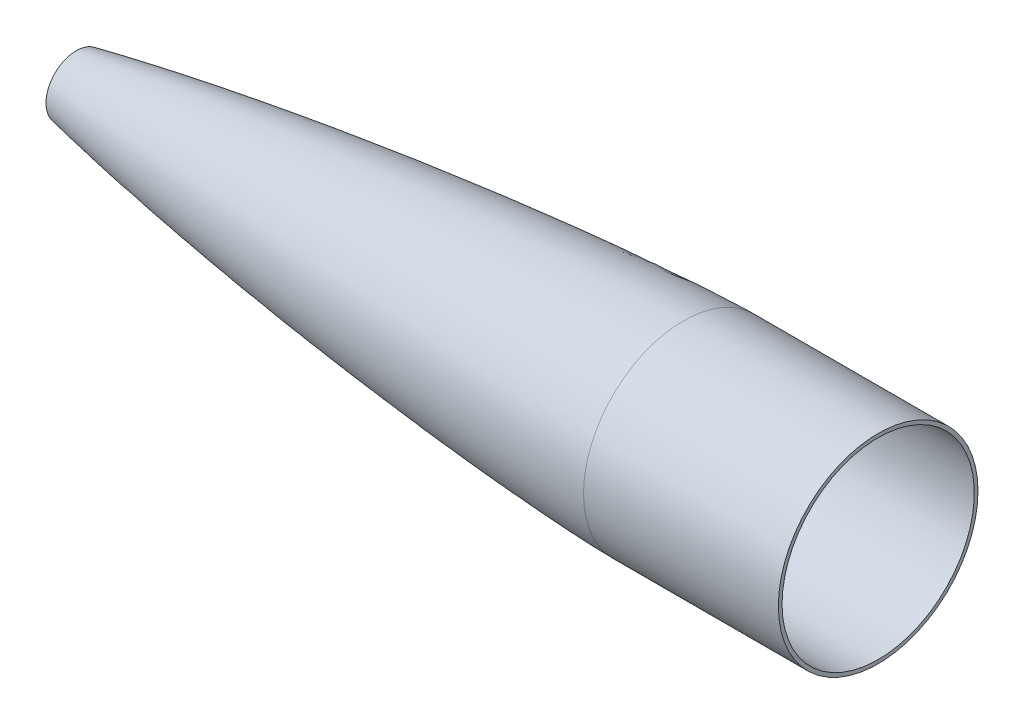
SolidWorks part; units mm, degrees
material "G12 Fiberglass"
ref_plane "Front Plane" through (0, 0, 0) normal (0, 0, 1) x (1, 0, 0)
ref_plane "Top Plane" through (0, 0, 0) normal (0, 1, 0) x (1, 0, 0)
ref_plane "Right Plane" through (0, 0, 0) normal (1, 0, 0) x (0, 0, -1)
sketch "Sketch1" plane through (0, 0, 0) normal (0, 0, 1) x (1, 0, 0)
  line L1 (0, 0) -> (294.4368, 0)
  line L6 (294.4368, 0) -> (374.4614, 0)
  line L7 (374.4614, 0) -> (374.4614, 41.1)
  line L8 (374.4614, 41.1) -> (294.2481, 41.1)
  spline S0 degree 4 poles (0, 0) (0.0018, 0.0062) (0.0065, 0.0183) (0.02, 0.0405) (0.0516, 0.0816) (0.098, 0.1304) (0.1591, 0.1863) (0.2472, 0.2588) (0.369, 0.3497) (0.5547, 0.4751) (0.869, 0.666) (1.3994, 0.9536) (2.3272, 1.3982) (4.009, 2.1055) (7.0408, 3.2125) (12.0632, 4.8001) (21.111, 7.2896) (33.8929, 10.3082) (49.7554, 13.609) (67.9644, 16.9948) (86.2568, 20.0969) (104.5881, 22.9593) (122.9505, 25.6145) (141.3391, 28.0808) (159.7506, 30.3703) (178.1826, 32.4881) (196.6334, 34.4348) (215.102, 36.2057) (233.5875, 37.7898) (252.0898, 39.1673) (267.7728, 40.127) (279.7318, 40.6956) (287.9596, 40.9757) (291.5527, 41.062) (293.3496, 41.093) (294.2481, 41.1) knots 0 0 0 0 0 0.000087 0.000174 0.000347 0.000695 0.00099 0.001284 0.001879 0.002733 0.003996 0.006219 0.009974 0.016536 0.028475 0.049524 0.080651 0.142462 0.204716 0.266969 0.329223 0.391477 0.453731 0.515984 0.578238 0.640492 0.702745 0.764999 0.827253 0.889506 0.95176 0.97588 0.98794 1 1 1 1 1 construction
  spline S1 degree 4 poles (0, 0) (0.0018, 0.0062) (0.0065, 0.0183) (0.02, 0.0405) (0.0516, 0.0816) (0.098, 0.1304) (0.1591, 0.1863) (0.2472, 0.2588) (0.369, 0.3497) (0.5547, 0.4751) (0.869, 0.666) (1.3994, 0.9536) (2.3272, 1.3982) (4.009, 2.1055) (7.0408, 3.2125) (12.0632, 4.8001) (21.111, 7.2896) (33.8929, 10.3082) (49.7554, 13.609) (67.9644, 16.9948) (86.2568, 20.0969) (104.5881, 22.9593) (122.9505, 25.6145) (141.3391, 28.0808) (159.7506, 30.3703) (178.1826, 32.4881) (196.6334, 34.4348) (215.102, 36.2057) (233.5875, 37.7898) (252.0898, 39.1673) (267.7728, 40.127) (279.7318, 40.6956) (287.9596, 40.9757) (291.5527, 41.062) (293.3496, 41.093) (294.2481, 41.1) knots 0 0 0 0 0 0.000087 0.000174 0.000347 0.000695 0.00099 0.001284 0.001879 0.002733 0.003996 0.006219 0.009974 0.016536 0.028475 0.049524 0.080651 0.142462 0.204716 0.266969 0.329223 0.391477 0.453731 0.515984 0.578238 0.640492 0.702745 0.764999 0.827253 0.889506 0.95176 0.97588 0.98794 1 1 1 1 1
  dimension "D1" = 80.2133
  dimension "D2" = 41.1
  dimension "D3" = 294.4368
ref_axis "Axis1" through (27.957, 0, 0) along (1, 0, 0)
revolve "Revolve1" add sketch "Sketch1" angle 360 about axis through (27.957, 0, 0) along (1, 0, 0)
shell "Shell1" thickness 1.524 removed face at (374.4614, 0, 41.1)
ref_plane "Plane1" through (44.2614, 0, 0) normal (1, 0, 0) x (0, 0, -1)
sketch "Sketch6" plane through (44.2614, 0, 0) normal (1, 0, 0) x (0, 0, -1)
  circle A1 centre (0, 0) radius 14.5845
extrude "Cut-Extrude1" cut sketch "Sketch6" against normal blind 98.044
ref_plane "Plane2" through (294.2482, 0, 0) normal (1, 0, 0) x (0, 0, -1)
equation "\"S2_S_Airframe_ID\"= 3"
equation "\"S2_S_Airframe_Thickness\"= 0.11811"
equation "\"S2_B_Airframe_ID\"= 3.5"
equation "\"S2_B_Airframe_Thickness\"= 0.11811"
equation "\"S2_B_Airframe_Aft_Length\"= 30"
equation "\"S2_B_Airframe_Forward_Length\"= 3"
equation "\"S2_C_Coupler_Length\"= 6"
equation "\"S2_S_Airframe_Aft_Length\"= 32"
equation "\"S2_S_Airframe_Forward_Length\"= 16"
equation "\"D2@Sketch1\"=\"S2_S_Airframe_ID\"/2+\"S2_S_Airframe_Thickness\""
